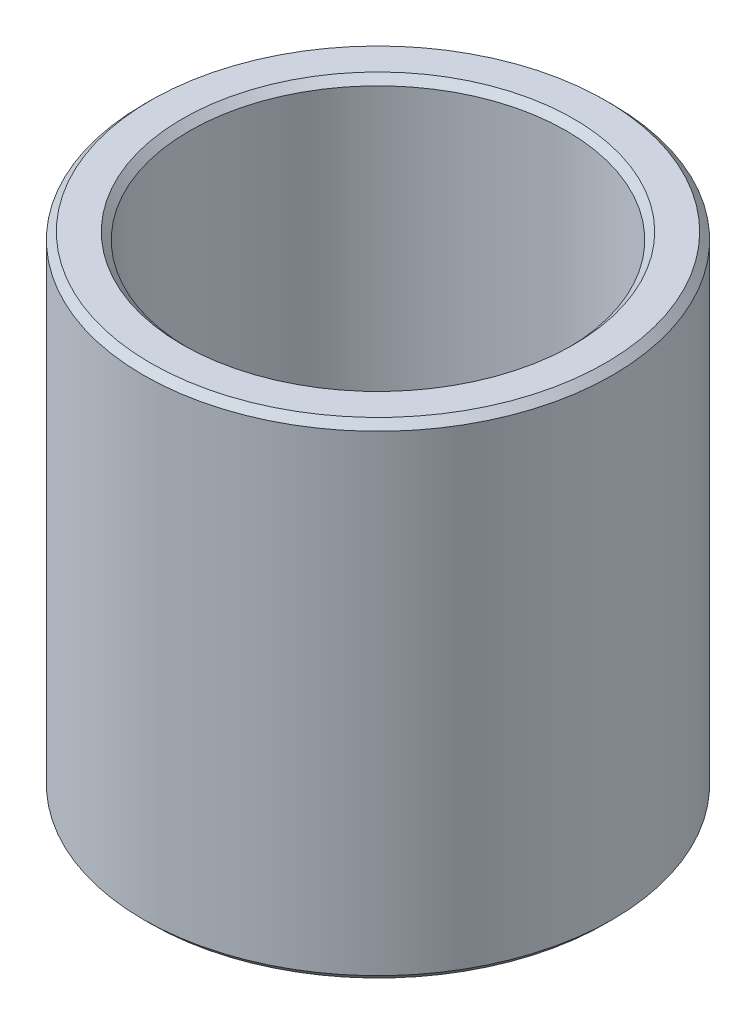
SolidWorks part; units mm, degrees
ref_plane "Front Plane" through (0, 0, 0) normal (0, 0, 1) x (1, 0, 0)
ref_plane "Top Plane" through (0, 0, 0) normal (0, 1, 0) x (1, 0, 0)
ref_plane "Right Plane" through (0, 0, 0) normal (1, 0, 0) x (0, 0, -1)
sketch "Sketch1" plane through (0, 0, 0) normal (0, 1, 0) x (1, 0, 0)
  circle A0 centre (0, 0) radius 42.5
  dimension "SLEEVE_OD" = 85
extrude "Boss-Extrude1" add sketch "Sketch1" along normal blind 87.99
sketch "Sketch2" plane through (0, 0, 0) normal (0, 1, 0) x (1, 0, 0)
  circle A0 centre (0, 0) radius 34.1883
  dimension "BORE_D" = 68.3765
extrude "Cut-Extrude1" cut sketch "Sketch2" along normal through all
chamfer "Chamfer1" distance 1.2746 angle 45 4 edges at (0, 87.99, 34.1883) (0, 0, 34.1883) (0, 0, 42.5) (0, 87.99, 42.5)
